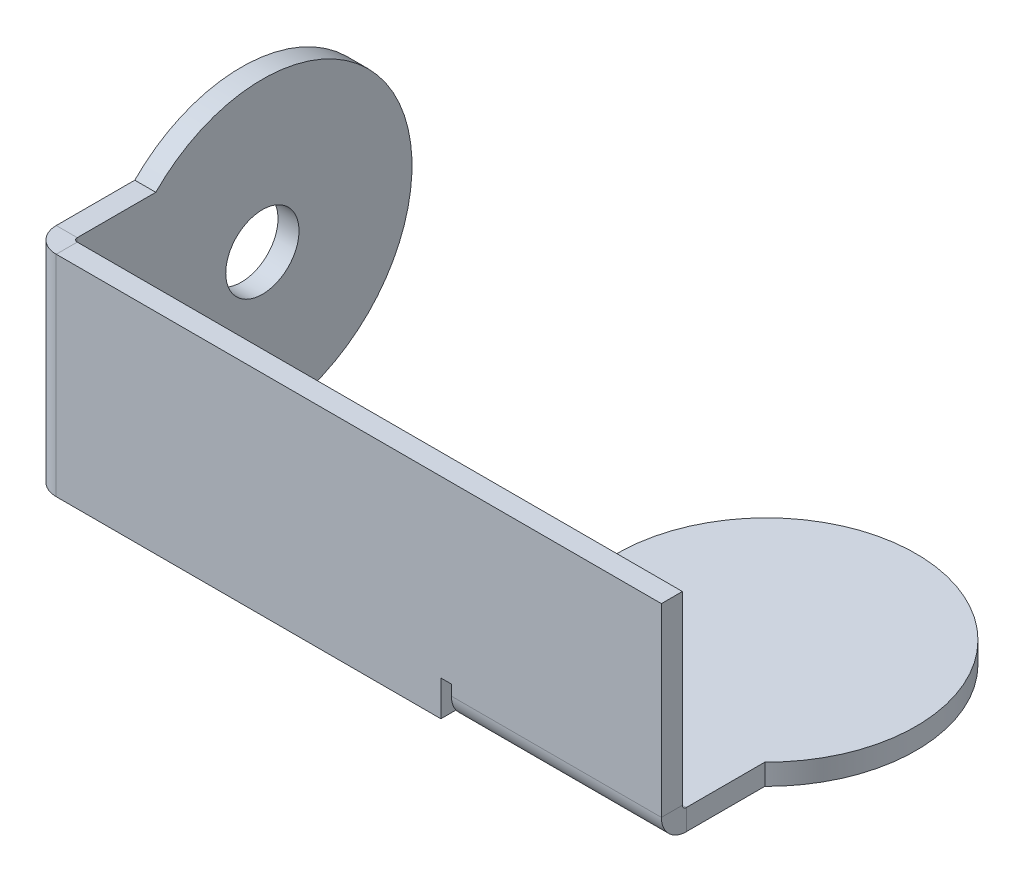
SolidWorks part; units mm, degrees
note: The reader was unsure of these and kept them because the rebuilt part matched: flange length of "边线-法兰1", "边线-法兰2".
ref_plane "前视基准面" through (0, 0, 0) normal (0, 0, 1) x (1, 0, 0)
ref_plane "上视基准面" through (0, 0, 0) normal (0, 1, 0) x (1, 0, 0)
ref_plane "右视基准面" through (0, 0, 0) normal (1, 0, 0) x (0, 0, -1)
sketch "草图1" plane through (0, 0, 0) normal (0, 0, 1) x (1, 0, 0)
  line L1 (60, 20) -> (-60, 20)
  line L2 (60, 20) -> (60, -20)
  line L3 (60, -20) -> (-60, -20)
  line L4 (-60, 20) -> (-60, -20)
  line L5 (60, 20) -> (-60, -20) construction
  line L6 (60, -20) -> (-60, 20) construction
  point P0 (0, 0)
  dimension "D1" = 40
  dimension "D2" = 120
base flange "基体-法兰1" sketch "草图1" thickness 4 reverse thickness direction no parameters "D1"=0.7366
edge flange "边线-法兰1" sketch "草图10" flange angle 90 flange length 36 flange position material inside bend radius 0.7366 thickness 4 relief rectangular parameters "D6"=10, "D8"=1
sketch "草图10" plane through (-60, 0, -4) normal (1, 0, 0) x (0, -1, 0)
  line L2 (-20, 0) -> (-20, 32)
  line L3 (-20, 32) -> (20, 32)
  line L4 (20, 32) -> (20, 0)
  line L5 (20, 0) -> (-20, 0) construction
  line L6 (20, 0) -> (-20, 0)
bend "边线折弯1" bend radius 0.7366 bend angle 90 parameters "D5"=1
sketch "草图12" plane through (-60, 0, 0) normal (-1, 0, 0) x (0, 0, 1)
  line L0 (0, 0) -> (-40, 0) construction
  circle A0 centre (-40, 0) radius 28.5
  dimension "D1" = 57
  dimension "D2" = 40
extrude "凸台-拉伸1" add sketch "草图12" against normal blind 4
sketch "草图13" plane through (-60, 0, 0) normal (-1, 0, 0) x (0, 0, 1)
  circle A0 centre (-40, 0) radius 6.9798
  dimension "D1" = 13.9595
extrude "切除-拉伸2" cut sketch "草图13" against normal blind 4 normal cut yes
edge flange "边线-法兰2" sketch "草图16" flange angle 90 flange length 34 flange position material inside bend radius 0.7366 thickness 4 relief rectangular parameters "D6"=10
sketch "草图16" plane through (0, -20, -4) normal (0, 1, 0) x (1, 0, 0)
  line L2 (20, 0) -> (20, 30)
  line L3 (20, 30) -> (60, 30)
  line L4 (60, 30) -> (60, 0)
  line L5 (60, 0) -> (-55.2634, 0) construction
  line L6 (60, 0) -> (20, 0)
  line L7 (-55.2634, 0) -> (60, 0) construction
  dimension "D1" = 40
bend "边线折弯2" bend radius 0.7366 bend angle 90 parameters "D5"=2
sketch "草图17" plane through (0, -20, 0) normal (0, -1, 0) x (1, 0, 0)
  line L0 (40, -34) -> (40, -40) construction
  line L1 (60, -34) -> (20, -34) construction
  line L2 (-55.2634, 0) -> (18, 0) construction
  circle A0 centre (40, -40) radius 28.5
  dimension "D2" = 57
  dimension "D1" = 40
extrude "凸台-拉伸2" add sketch "草图17" against normal blind 4
sketch "折弯-线1" plane through (0, 0, 0) normal (0, 1, 0) x (1, 0, 0)
sketch "边界框1" plane through (0, 0, 0) normal (0, 1, 0) x (1, 0, 0)
sheet metal parameters "钣金6" thickness 4 parameters "D1"=0.7366
flat pattern "平板型式6" [suppressed]
sketch "折弯-线2" plane through (0, 0, 0) normal (0, 1, 0) x (1, 0, 0)
sketch "边界框2" [suppressed] plane through (0, 0, 0) normal (0, 1, 0) x (1, 0, 0)
sheet metal parameters "钣金7" thickness 4 parameters "D1"=0.7366
flat pattern "平板型式6" [suppressed]
sketch "折弯-线2" plane through (0, 0, 0) normal (0, 1, 0) x (1, 0, 0)
sketch "边界框2" [suppressed] plane through (0, 0, 0) normal (0, 1, 0) x (1, 0, 0)
bend of the flat pattern "展平-<边线折弯1>1"
sheet metal parameters "钣金9" thickness 4 parameters "D1"=0.7366
flat pattern "平板型式6" [suppressed]
sketch "折弯-线2" plane through (0, 0, 0) normal (0, 1, 0) x (1, 0, 0)
sketch "边界框2" [suppressed] plane through (0, 0, 0) normal (0, 1, 0) x (1, 0, 0)
bend of the flat pattern "展平-<边线折弯1>1"
sheet metal parameters "钣金10" thickness 4 parameters "D1"=0.7366
flat pattern "平板型式6" [suppressed]
sketch "折弯-线2" plane through (0, 0, 0) normal (0, 1, 0) x (1, 0, 0)
sketch "边界框2" [suppressed] plane through (0, 0, 0) normal (0, 1, 0) x (1, 0, 0)
bend of the flat pattern "展平-<边线折弯1>1"
sheet metal parameters "钣金12" thickness 4 parameters "D1"=0.7366
flat pattern "平板型式6" [suppressed]
sketch "折弯-线2" plane through (0, 0, 0) normal (0, 1, 0) x (1, 0, 0)
sketch "边界框2" [suppressed] plane through (0, 0, 0) normal (0, 1, 0) x (1, 0, 0)
bend of the flat pattern "展平-<边线折弯1>1"
bend of the flat pattern "展平-<边线折弯2>1"
sheet metal parameters "钣金13" thickness 4 parameters "D1"=0.7366
flat pattern "平板型式6" [suppressed]
sketch "折弯-线2" plane through (0, 0, 0) normal (0, 1, 0) x (1, 0, 0)
sketch "边界框2" [suppressed] plane through (0, 0, 0) normal (0, 1, 0) x (1, 0, 0)
bend of the flat pattern "展平-<边线折弯1>1"
bend of the flat pattern "展平-<边线折弯2>1"
